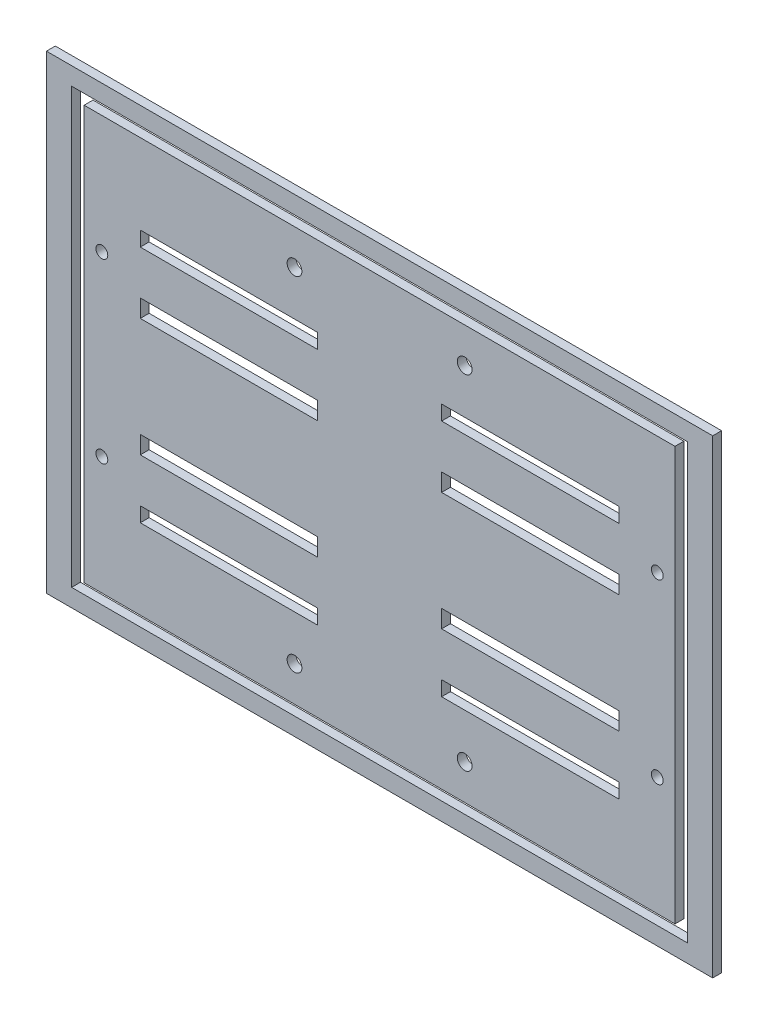
SolidWorks part; units mm, degrees
ref_plane "Front" through (0, 0, 0) normal (0, 0, 1) x (1, 0, 0)
ref_plane "Top" through (0, 0, 0) normal (0, 1, 0) x (1, 0, 0)
ref_plane "Right" through (0, 0, 0) normal (1, 0, 0) x (0, 0, -1)
sketch "草图2" plane through (0, 0, 0) normal (0, 0, 1) x (1, 0, 0)
  line L1 (-100, -70) -> (100, -70)
  line L2 (-100, -70) -> (-100, 70)
  line L3 (-100, 70) -> (100, 70)
  line L4 (100, -70) -> (100, 70)
  line L5 (-100, -70) -> (100, 70) construction
  line L6 (-100, 70) -> (100, -70) construction
  point P0 (0, 0)
  dimension "D1" = 140
  dimension "D2" = 200
extrude "凸台-拉伸1" add sketch "草图2" along normal blind 3
sketch "草图3" plane through (0, 0, 3) normal (0, 0, 1) x (1, 0, 0)
  line L0 (94, -30) -> (94, 30) construction
  line L2 (100, -70) -> (100, 70) construction
  circle A0 centre (94, 30) radius 2
  circle A1 centre (94, -30) radius 2
  point P4 (94, 0)
  dimension "D1" = 4
  dimension "D2" = 60
  dimension "D3" = 6
extrude "切除-拉伸1" cut sketch "草图3" against normal blind 3 contours A0 | A1
sketch "草图4" plane through (0, 0, 3) normal (0, 0, 1) x (1, 0, 0)
  line L0 (-100, 0) -> (100, 0) construction
  line L1 (-100, 70) -> (-100, -70) construction
  line L2 (100, -70) -> (100, 70) construction
  line L4 (21, 23) -> (81, 23)
  line L5 (21, 23) -> (21, 17)
  line L6 (21, 17) -> (81, 17)
  line L7 (81, 23) -> (81, 17)
  line L8 (21, 23) -> (81, 17) construction
  line L9 (21, 17) -> (81, 23) construction
  line L10 (21, -23) -> (81, -23)
  line L11 (21, -23) -> (21, -17)
  line L12 (21, -17) -> (81, -17)
  line L13 (81, -23) -> (81, -17)
  line L14 (21, -23) -> (81, -17) construction
  line L15 (21, -17) -> (81, -23) construction
  point P6 (51, 20)
  point P11 (51, -20)
  dimension "D1" = 34
  dimension "D2" = 6
  dimension "D3" = 6
  dimension "D4" = 17
  dimension "D5" = 60
  dimension "D6" = 19
extrude "切除-拉伸2" cut sketch "草图4" against normal blind 10
sketch "草图5" plane through (0, 0, 0) normal (0, 0, -1) x (-1, 0, 0)
  line L0 (-21, 17) -> (-21, 23) construction
  line L1 (-81, 37.9088) -> (-21, 37.9088)
  line L2 (-81, 37.9088) -> (-81, 42.9088)
  line L3 (-81, 42.9088) -> (-21, 42.9088)
  line L4 (-21, 37.9088) -> (-21, 42.9088)
  line L5 (-81, 37.9088) -> (-21, 42.9088) construction
  line L6 (-81, 42.9088) -> (-21, 37.9088) construction
  line L7 (-81, 23) -> (-81, 17) construction
  point P0 (-51, 40.4088)
  dimension "D1" = 5
extrude "切除-拉伸3" cut sketch "草图5" against normal blind 6
mirror "镜向1" about plane through (0, 0, 0) normal (0, 1, 0) of "切除-拉伸3"
ref_plane "基准面1" through (0, 0, 0) normal (-1, 0, 0) x (0, 0, 1)
mirror "镜向2" about plane through (0, 0, 0) normal (-1, 0, 0) of "切除-拉伸1", "镜向1", "切除-拉伸2", "切除-拉伸3"
sketch "草图6" plane through (0, 0, 3) normal (0, 0, 1) x (1, 0, 0)
  circle A0 centre (-28.8, 58.1086) radius 2.5 construction
  circle A1 centre (-28.8, 58.1086) radius 2.5
  circle A2 centre (-28.8, -58.1086) radius 2.5 construction
  circle A3 centre (28.8, -58.1086) radius 2.5 construction
  circle A4 centre (28.8, 58.1086) radius 2.5 construction
  circle A5 centre (-28.8, -58.1086) radius 2.5
  circle A6 centre (28.8, -58.1086) radius 2.5
  circle A7 centre (28.8, 58.1086) radius 2.5
extrude "切除-拉伸4" cut sketch "草图6" against normal blind 5
sketch "草图7" plane through (0, 0, 3) normal (0, 0, 1) x (1, 0, 0)
  point P0 (-100, -70)
sketch "草图9" plane through (0, 0, 3) normal (0, 0, 1) x (1, 0, 0)
  line L1 (-112.7639, -79.4676) -> (112.7639, -79.4676)
  line L2 (-112.7639, -79.4676) -> (-112.7639, 79.4676)
  line L3 (-112.7639, 79.4676) -> (112.7639, 79.4676)
  line L4 (112.7639, -79.4676) -> (112.7639, 79.4676)
  line L5 (-112.7639, -79.4676) -> (112.7639, 79.4676) construction
  line L6 (-112.7639, 79.4676) -> (112.7639, -79.4676) construction
  line L7 (-104.2357, -73.4576) -> (104.2357, -73.4576)
  line L8 (-104.2357, -73.4576) -> (-104.2357, 73.4576)
  line L9 (-104.2357, 73.4576) -> (104.2357, 73.4576)
  line L10 (104.2357, -73.4576) -> (104.2357, 73.4576)
  line L11 (-104.2357, -73.4576) -> (104.2357, 73.4576) construction
  line L12 (-104.2357, 73.4576) -> (104.2357, -73.4576) construction
  point P0 (0, 0)
  point P6 (0, 0)
extrude "凸台-拉伸2" add sketch "草图9" against normal up to surface (3 mm away) separate body contours L2 L3 L4 L1 | L8 L9 L10 L7 up to face at (-31.3, -58.1086, 0)
